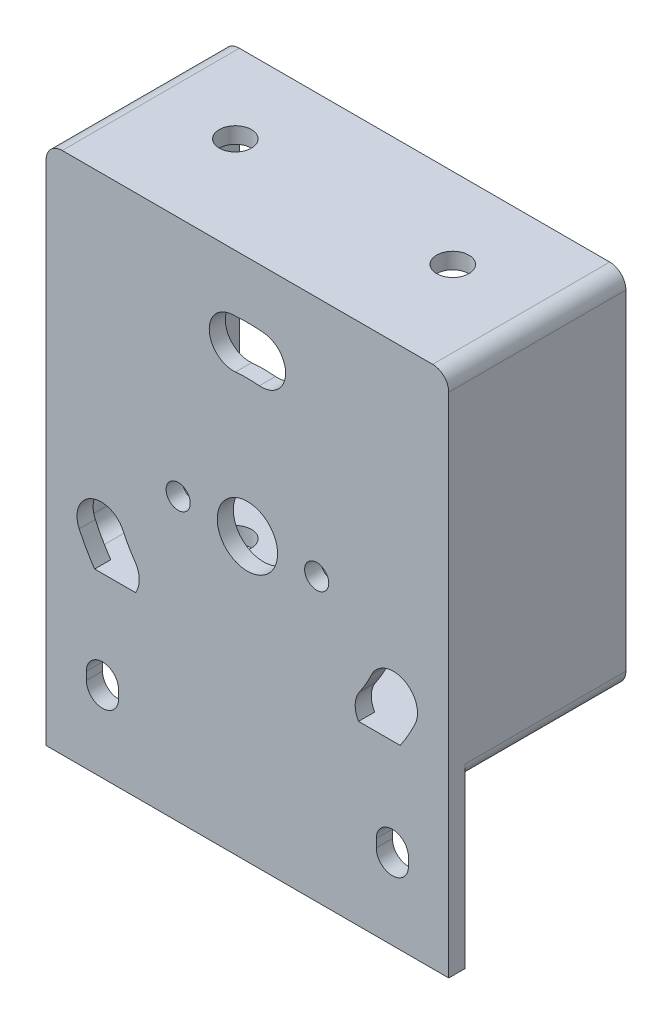
SolidWorks part; units mm, degrees
note: The reader was unsure of these and kept them because the rebuilt part matched: shared geometry of "Sketch15<3>".
ref_plane "Front Plane" through (0, 0, 0) normal (0, 0, 1) x (1, 0, 0)
ref_plane "Top Plane" through (0, 0, 0) normal (0, 1, 0) x (1, 0, 0)
ref_plane "Right Plane" through (0, 0, 0) normal (1, 0, 0) x (0, 0, -1)
sketch "Sketch9" plane through (0, 0, 0) normal (0, 0, 1) x (1, 0, 0)
  line L0 (0, 0) -> (50, 0)
  line L1 (50, 0) -> (50, 50)
  line L2 (50, 50) -> (0, 50)
  line L3 (0, 50) -> (0, 0)
  line L4 (7, 10) -> (7, 9.5)
  line L5 (43, 10) -> (43, 10.5)
  line L6 (7, 10) -> (7, 10.5)
  line L7 (9, 9.5) -> (9, 10.5)
  line L8 (43, 10) -> (43, 9.5)
  line L9 (5, 10.5) -> (5, 9.5)
  line L10 (45, 9.5) -> (45, 10.5)
  line L11 (41, 10.5) -> (41, 9.5)
  circle A0 centre (25, 35) radius 3.75
  circle A1 centre (16.4, 35) radius 1.5
  circle A2 centre (33.6, 35) radius 1.5
  circle A3 centre (25, 35) radius 23.5
  arc A9 (9, 10.5) -> (5, 10.5) centre (7, 10.5) ccw
  arc A11 (45, 10.5) -> (41, 10.5) centre (43, 10.5) ccw
  arc A12 (5, 9.5) -> (9, 9.5) centre (7, 9.5) ccw
  arc A13 (41, 9.5) -> (45, 9.5) centre (43, 9.5) ccw
  dimension "D4" = 7.5
  dimension "D10" = 47
  dimension "D12" = 10
  dimension "D13" = 7
  dimension "D14" = 10
  dimension "D19" = 4
  dimension "D20" = 0.5
  dimension "D22" = 4
  dimension "D23" = 4
  dimension "D1" = 50
  dimension "D2" = 50
  dimension "D3" = 15
  dimension "D5" = 25
  dimension "D6" = 8.6
  dimension "D7" = 8.6
  dimension "D8" = 15
  dimension "D9" = 15
  dimension "D11" = 7
  dimension "D17" = 0.5
  dimension "D18" = 0.5
  dimension "D21" = 0.5
extrude "Boss-Extrude2" add sketch "Sketch9" along normal blind 2
sketch "Sketch11" plane through (0, 0, 0) normal (0, 0, -1) x (-1, 0, 0)
  line L1 (0, 0) -> (-50, 0) construction
  line L2 (0, 20) -> (-21.5, 20)
  line L3 (-50, 0) -> (-50, 50) construction
  line L4 (-7, 20) -> (0, 20)
  line L5 (0, 50) -> (0, 0) construction
  line L6 (-50, 20) -> (-28.5, 20)
  line L7 (-50, 20) -> (-28.5, 20)
  line L8 (-28.5, 20) -> (-28.5, 22)
  line L9 (-28.5, 22) -> (-48, 22)
  line L10 (-48, 22) -> (-48, 50)
  line L11 (-50, 50) -> (0, 50) construction
  line L12 (-21.5, 20) -> (-21.5, 22)
  line L13 (-21.5, 22) -> (-2, 22)
  line L14 (-2, 22) -> (-2, 50)
  line M11 (-50, 50) -> (-50, 0)
  line M13 (0, 0) -> (0, 50)
  line M14 (0, 50) -> (-50, 50)
  dimension "D2" = 20
  dimension "D3" = 21.5
  dimension "D4" = 21.5
  dimension "D5" = 2
  dimension "D6" = 2
  dimension "D7" = 2
  dimension "D8" = 2
extrude "Boss-Extrude3" add sketch "Sketch11" along normal blind 20 contours L9 L10 L6 L8 M14 M11 | L14 L13 L12 L2 M13 M14
sketch "Sketch12" plane through (0, 22, 0) normal (0, 1, 0) x (1, 0, 0)
  line L0 (28.5, 20) -> (48, 20) construction
  line L1 (28.5, 20) -> (28.5, 0) construction
  circle A0 centre (38.5, 10) radius 2
  dimension "D1" = 4
  dimension "D2" = 10
  dimension "D3" = 10
extrude "Cut-Extrude1" cut sketch "Sketch12" against normal blind 2 contours A0
sketch "Sketch13" plane through (0, 22, 0) normal (0, 1, 0) x (1, 0, 0)
  line L0 (21.5, 20) -> (2, 20) construction
  line L1 (21.5, 20) -> (21.5, 0) construction
  circle A0 centre (11.5, 10) radius 2
  dimension "D1" = 4
  dimension "D2" = 10
  dimension "D3" = 10
extrude "Cut-Extrude2" cut sketch "Sketch13" against normal blind 2 and the other way blind 50
sketch "Sketch15" plane through (0, 0, 2) normal (0, 0, 1) x (1, 0, 0)
  line L0 (0, 65) -> (50, 65)
  line L2 (0, 65) -> (0, 50)
  line L4 (50, 65) -> (50, 50)
  arc A16 (26.4816, 51.9353) -> (23.5184, 51.9353) centre (25, 35) ccw
  arc A17 (27.0046, 57.9125) -> (22.9954, 57.9125) centre (25, 35) ccw
  arc A27 (22.9954, 57.9125) -> (23.5184, 51.9353) centre (23.2569, 54.9239) ccw
  arc A28 (26.4816, 51.9353) -> (27.0046, 57.9125) centre (26.7431, 54.9239) ccw
  arc A34 (6.1015, 21.8909) -> (11.0316, 25.3107) centre (8.5665, 23.6008) ccw
  arc A38 (9.5612, 27.8835) -> (4.1123, 25.3718) centre (6.8368, 26.6276) ccw
  arc A40 (4.1123, 25.3718) -> (6.1015, 21.8909) centre (25, 35) ccw
  arc A43 (9.5612, 27.8835) -> (11.0316, 25.3107) centre (25, 35) ccw
  arc A66 (38.9256, 25.2492) -> (43.8405, 21.8077) centre (41.383, 23.5285) ccw
  arc A69 (26.4816, 51.9353) -> (23.5184, 51.9353) centre (25, 35) ccw
  arc A72 (9.5612, 27.8835) -> (11.0316, 25.3107) centre (25, 35) ccw
  arc A73 (27.0046, 57.9125) -> (22.9954, 57.9125) centre (25, 35) ccw
  arc A74 (26.4816, 51.9353) -> (23.5184, 51.9353) centre (25, 35) ccw
  arc A75 (27.0046, 57.9125) -> (22.9954, 57.9125) centre (25, 35) ccw
  arc A76 (43.8405, 21.8077) -> (45.8451, 25.2798) centre (25, 35) ccw
  arc A77 (38.9256, 25.2492) -> (40.4072, 27.8155) centre (25, 35) ccw
  arc A78 (4.1123, 25.3718) -> (6.1015, 21.8909) centre (25, 35) ccw
  arc A94 (45.8451, 25.2798) -> (40.4072, 27.8155) centre (43.1262, 26.5476) ccw
  dimension "D2" = 6
  dimension "D11" = 17
  dimension "D13" = 6
  dimension "D14" = 6
  dimension "D8" = 20
  dimension "D9" = 20
  dimension "D10" = 15
extrude "Boss-Extrude4" add sketch "Sketch15" against normal blind 2
extrude "Cut-Extrude4" cut sketch "Sketch15<3>" against normal blind 2
sketch "Sketch15<3>" plane through (0, 0, 2) normal (0, 0, 1) x (1, 0, 0) same geometry as "Sketch15"
sketch "Sketch17" plane through (0, 0, 0) normal (0, 0, -1) x (-1, 0, 0)
  line L0 (-50, 63) -> (-50, 65)
  line L1 (-50, 65) -> (-50, 50) construction
  line L2 (-50, 63) -> (0, 63)
  line L3 (0, 65) -> (0, 50) construction
  line L4 (0, 65) -> (-50, 65) construction
  line L5 (-50, 65) -> (0, 65)
  line L6 (0, 65) -> (0, 63)
  dimension "D1" = 2
sketch "Sketch21" plane through (0, 0, 0) normal (0, 0, 1) x (1, 0, 0)
  line L0 (38.8016, 22) -> (43.9737, 22)
  arc A1 (38.8016, 22) -> (43.9645, 22) centre (41.383, 23.5285) ccw
  arc M2 (38.8016, 22) -> (43.8405, 21.8077) centre (41.383, 23.5285) ccw
extrude "Boss-Extrude7" add sketch "Sketch21" along normal blind 2 contours A1 L0 M2
sketch "Sketch24" plane through (0, 0, 0) normal (0, 0, 1) x (1, 0, 0)
  line L0 (11.1037, 22) -> (6.0263, 22)
  arc A0 (6.0293, 22) -> (11.1037, 22) centre (8.5665, 23.6008) ccw
  arc M4 (6.1015, 21.8909) -> (11.1037, 22) centre (8.5665, 23.6008) ccw
  line M5 (11.1037, 22) -> (6.0263, 22)
extrude "Boss-Extrude8" add sketch "Sketch24" along normal blind 2 contours A0 M5 M4
extrude "Boss-Extrude5" add sketch "Sketch17" along normal blind 20
sketch "Sketch19" plane through (0, 65, 0) normal (0, 1, 0) x (1, 0, 0)
  line L0 (0, 20) -> (50, 20) construction
  circle A0 centre (38.5, 10) radius 2
  circle A1 centre (38.5, 10) radius 2 construction
  circle A2 centre (11.5, 10) radius 2
  circle A3 centre (11.5, 10) radius 2 construction
  dimension "D1" = 4
  dimension "D4" = 4
  dimension "D2" = 0
  dimension "D3" = 0
  dimension "D5" = 0
  dimension "D6" = 10
extrude "Cut-Extrude5" cut sketch "Sketch19" against normal blind 49
sketch "Sketch20" plane through (0, 0, 0) normal (0, 0, -1) x (-1, 0, 0)
  line L0 (-50, 50) -> (-50, 63)
  line L1 (-50, 63) -> (-50, 50) construction
  line L2 (-50, 63) -> (-48, 63)
  line L3 (-50, 63) -> (0, 63) construction
  line L4 (-48, 63) -> (-48, 50)
  line L5 (0, 50) -> (0, 63)
  line L6 (0, 63) -> (-2, 63)
  line L7 (-2, 63) -> (-2, 50)
  line L8 (-2, 50) -> (0, 50)
  line L9 (-50, 63) -> (-48, 63)
  line M15 (0, 63) -> (-50, 63)
  line M16 (-50, 63) -> (-50, 50)
  line M17 (-50, 50) -> (-48, 50)
  line M29 (-2, 50) -> (0, 50)
  line M30 (0, 50) -> (0, 63)
extrude "Boss-Extrude6" add sketch "Sketch20" along normal blind 20 contours L4 M15 M16 M17 | L7 M15 M29 M30
fillet "Fillet2" radius 2 1 edges at (0, 65, -9)
fillet "Fillet3" radius 2 1 edges at (50, 65, -9)
fillet "Fillet5" radius 2 1 edges at (50, 20, -10)
fillet "Fillet6" radius 2 1 edges at (0, 20, -10)
fillet "Fillet7" radius 2 1 edges at (48, 63, -10)
fillet "Fillet8" radius 2 1 edges at (2, 22, -10)
fillet "Fillet9" radius 2 1 edges at (2, 63, -10)
fillet "Fillet10" radius 2 1 edges at (48, 22, -10)
